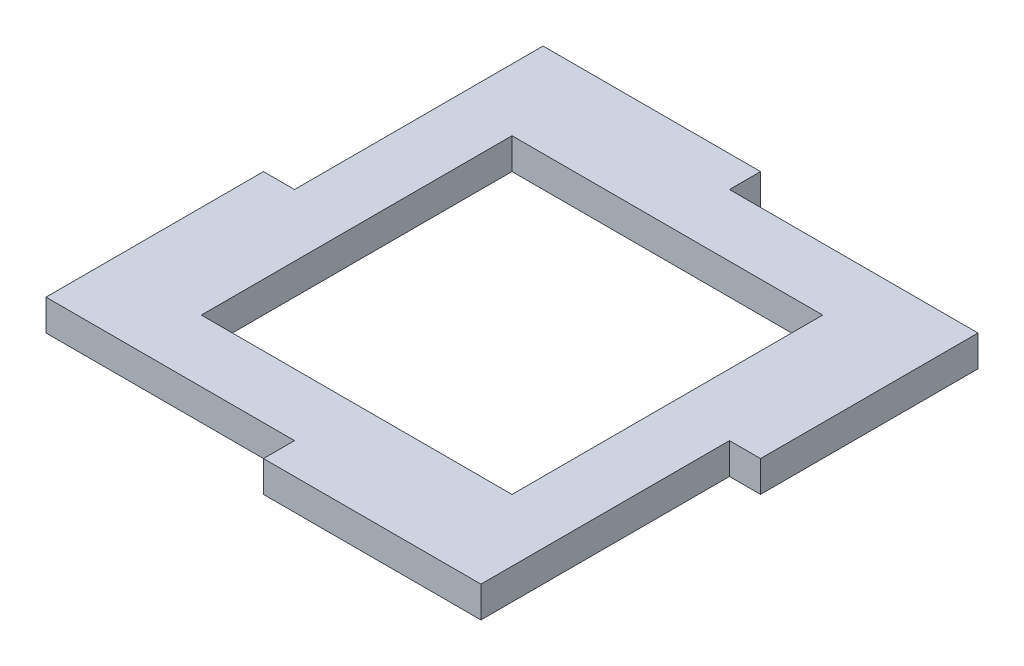
SolidWorks part; units mm, degrees
material "Acrylic (Medium-high impact)"
ref_plane "Front Plane" through (0, 0, 0) normal (0, 0, 1) x (1, 0, 0)
ref_plane "Top Plane" through (0, 0, 0) normal (0, 1, 0) x (1, 0, 0)
ref_plane "Right Plane" through (0, 0, 0) normal (1, 0, 0) x (0, 0, -1)
sketch "Sketch1" plane through (0, 0, 0) normal (0, 1, 0) x (1, 0, 0)
  line L0 (-112.5062, 93.3127) -> (-112.5062, 106.0127)
  line L1 (-112.5062, 93.3127) -> (65.2938, 93.3127)
  line L2 (-112.5062, 93.3127) -> (-112.5062, -84.4873)
  line L3 (-112.5062, -84.4873) -> (65.2938, -84.4873)
  line L4 (65.2938, 93.3127) -> (65.2938, -84.4873)
  line L5 (-112.5062, 106.0127) -> (-23.6062, 106.0127)
  line L6 (-23.6062, 106.0127) -> (-23.6062, 93.3127)
  line L7 (-112.5062, -84.4873) -> (-125.2062, -84.4873)
  line L8 (-125.2062, -84.4873) -> (-125.2062, 4.4127)
  line L9 (-125.2062, 4.4127) -> (-112.5062, 4.4127)
  line L10 (65.2938, -84.4873) -> (65.2938, -97.1873)
  line L11 (65.2938, -97.1873) -> (-23.6062, -97.1873)
  line L12 (-23.6062, -97.1873) -> (-23.6062, -84.4873)
  line L13 (65.2938, 93.3127) -> (77.9938, 93.3127)
  line L14 (77.9938, 93.3127) -> (77.9938, 4.4127)
  line L15 (77.9938, 4.4127) -> (65.2938, 4.4127)
  line L17 (39.8938, -59.0873) -> (-87.1062, -59.0873)
  line L18 (39.8938, -59.0873) -> (39.8938, 67.9127)
  line L19 (39.8938, 67.9127) -> (-87.1062, 67.9127)
  line L20 (-87.1062, -59.0873) -> (-87.1062, 67.9127)
  point P4 (-23.6062, 93.3127)
  point P5 (-112.5062, 4.4127)
  point P9 (65.2938, 4.4127)
  point P10 (-23.6062, -84.4873)
  dimension "D1" = 177.8
  dimension "D2" = 177.8
  dimension "D3" = 12.7
  dimension "D4" = 12.7
  dimension "D5" = 12.7
  dimension "D6" = 12.7
  dimension "D7" = 127
  dimension "D8" = 127
  dimension "D9" = 25.4
  dimension "D10" = 25.4
extrude "Boss-Extrude1" add sketch "Sketch1" along normal blind 12.7 contours L9 L8 L7 L2 | L6 L5 L0 L1 | L4 L1 L2 L3 | L15 L14 L13 L4 | L12 L11 L10 L3 region at (-68.0562, 0, -99.6627) region at (-68.0562, 0, -90.7982) region at (-118.8562, 0, 40.0373) region at (71.6438, 0, -48.8627) region at (20.8438, 0, 90.8373)
